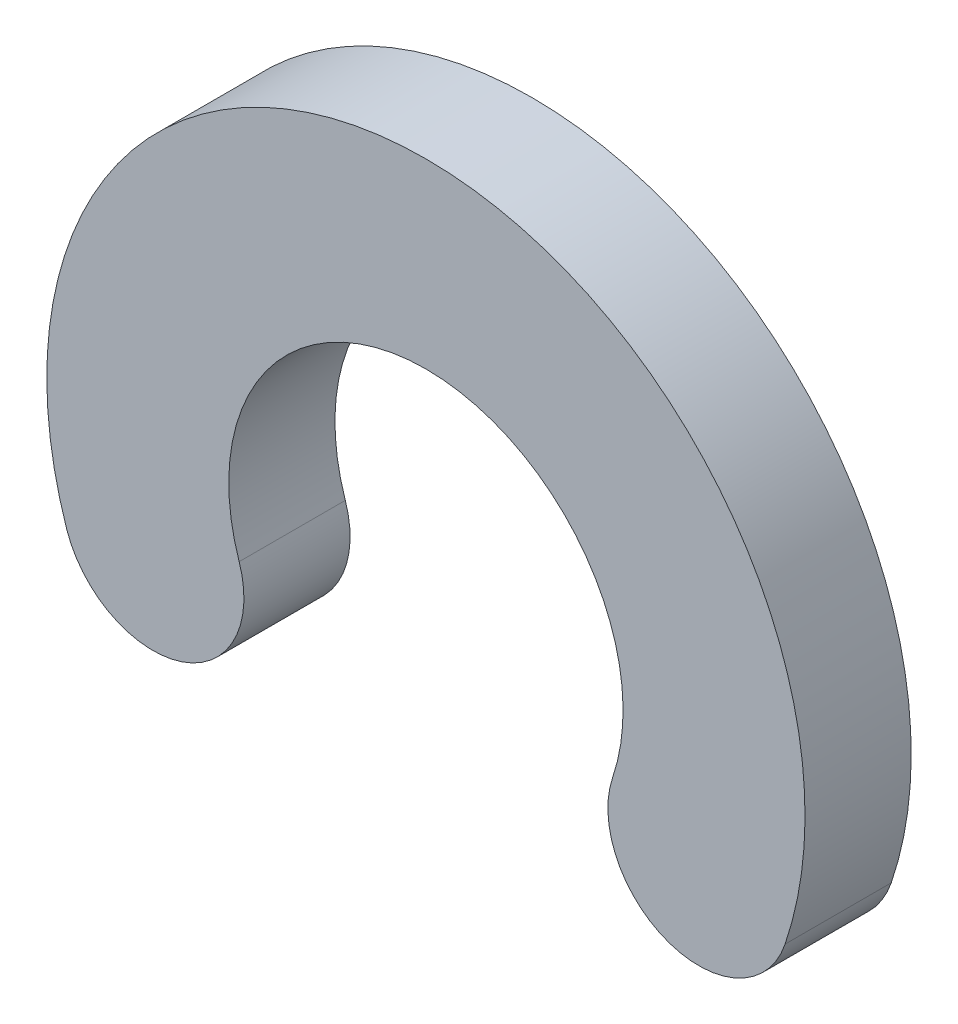
SolidWorks part; units mm, degrees
ref_plane "Front" through (0, 0, 0) normal (0, 0, 1) x (1, 0, 0)
ref_plane "Top" through (0, 0, 0) normal (0, 1, 0) x (1, 0, 0)
ref_plane "Right" through (0, 0, 0) normal (1, 0, 0) x (0, 0, -1)
sketch "Sketch1" plane through (0, 0, 0) normal (0, 0, 1) x (1, 0, 0)
  line L0 (0, 1.5089) -> (0, -1.7832) construction
  arc A0 (0.6158, -0.2081) -> (-0.6158, -0.2081) centre (0, 0) ccw
  arc A1 (1.1842, -0.4002) -> (-1.1842, -0.4002) centre (0, 0) ccw
  arc A2 (0.6158, -0.2081) -> (1.1842, -0.4002) centre (0.9, -0.3041) ccw
  arc A3 (-0.6158, -0.2081) -> (-1.1842, -0.4002) centre (-0.9, -0.3041) cw
  dimension "R" = 0.65
  dimension "r1" = 0.3
  dimension "B0" = 1.2
  dimension "b" = 0.6
extrude "Body" add sketch "Sketch1" against normal blind 0.35
